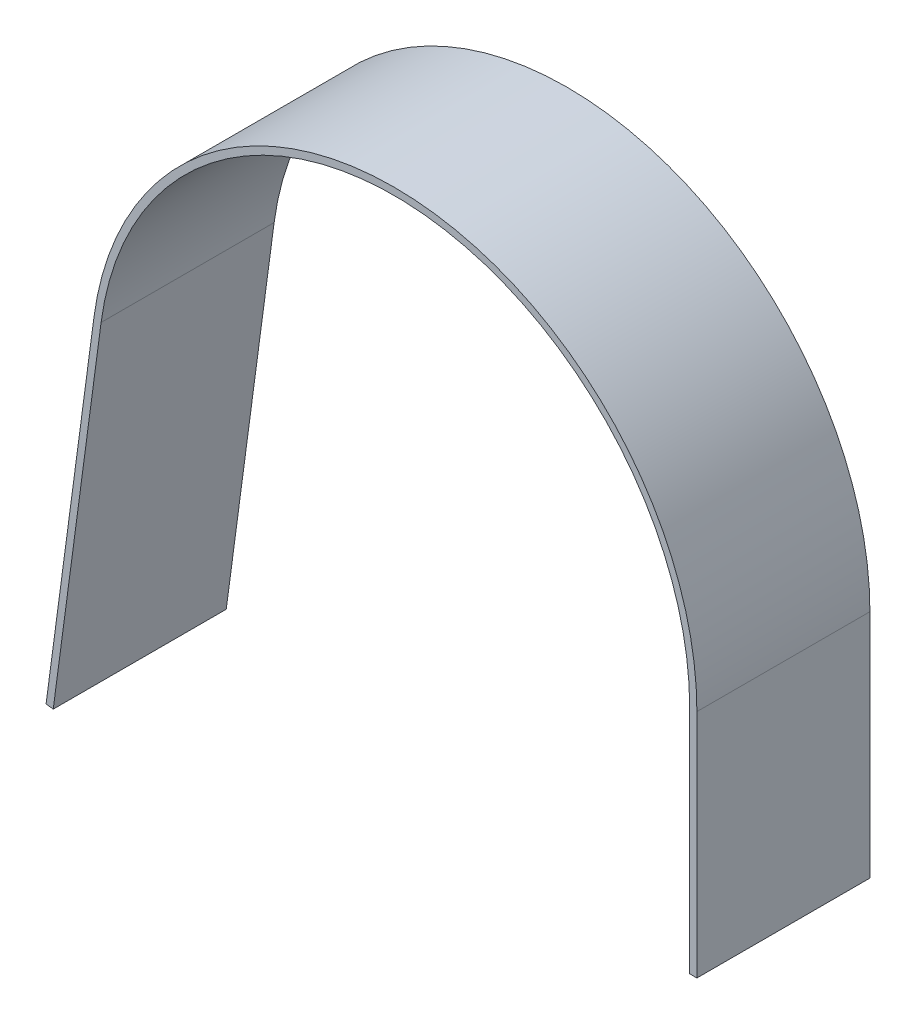
SolidWorks part; units mm, degrees
ref_plane "Front Plane" through (0, 0, 0) normal (0, 0, 1) x (1, 0, 0)
ref_plane "Top Plane" through (0, 0, 0) normal (0, 1, 0) x (1, 0, 0)
ref_plane "Right Plane" through (0, 0, 0) normal (1, 0, 0) x (0, 0, -1)
sketch "Sketch2" plane through (0, 0, 0) normal (0, 0, 1) x (1, 0, 0)
  line L0 (-7.5377, -7.4769) -> (-7.5377, 94.1231)
  line L1 (-7.5377, 94.1231) -> (-140.8877, 94.1231) construction
  line L2 (-273.0665, 111.7582) -> (-294.1502, -46.2676)
  line L3 (-7.5377, -7.4769) -> (-10.7127, -7.4769)
  line L4 (-10.7127, -7.4769) -> (-10.7127, 94.1231)
  line L5 (-273.0665, 111.7582) -> (-243.9815, 107.8777) construction
  line L6 (-269.9194, 111.3383) -> (-291.003, -46.6875)
  line L7 (-294.1502, -46.2676) -> (-291.003, -46.6875)
  arc A0 (-7.5377, 94.1231) -> (-273.0665, 111.7582) centre (-140.8877, 94.1231) ccw
  arc A1 (-10.7127, 94.1231) -> (-269.9194, 111.3383) centre (-140.8877, 94.1231) ccw
  arc A3 (-304.7615, -42.4304) -> (-304.7511, -17.0304) centre (-304.7563, -29.7304) ccw construction
  dimension "D1" = 101.6
  dimension "D2" = 133.35
  dimension "D3" = 3.175
extrude "Boss-Extrude1" add sketch "Sketch2" along normal blind 76.2
